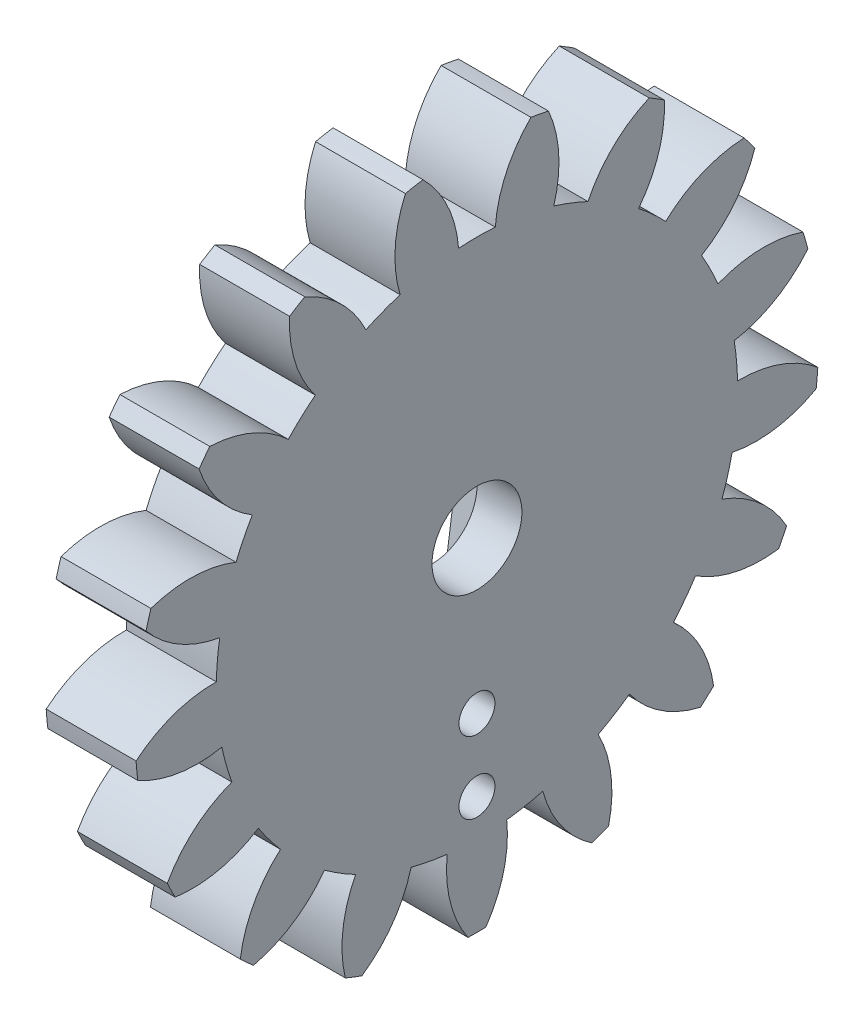
SolidWorks part; units mm, degrees
ref_plane "Plane1" through (0, 0, 0) normal (0, 0, 1) x (1, 0, 0)
ref_plane "Plane2" through (0, 0, 0) normal (0, 1, 0) x (1, 0, 0)
ref_plane "Plane3" through (0, 0, 0) normal (1, 0, 0) x (0, 0, -1)
sketch "HoldingSke" plane through (0, 0, 0) normal (0, 1, 0) x (1, 0, 0)
  line L0 (0, 0) -> (0.4782, -0.1462)
  line L1 (-15, 0) -> (100, 0) construction
  line L2 (0, 0) -> (-2.1039, 2.3779)
  line L3 (0, 0) -> (-11.863, 4.5341)
  line L4 (0, 0) -> (8.2586, 2.5249)
  line L5 (0, 0) -> (-46.8476, -17.4728)
  line L6 (0, 0) -> (-8.2896, -5.593)
  line L7 (-2.1039, 2.3779) -> (8.6588, 51.2067)
  line L8 (-76.2, 54.61) -> (-75.3, 54.61)
  line L9 (-71.009, 38.7566) -> (-53.1078, 45.2721)
  line L10 (-76.2, 71.12) -> (104.1128, 71.12)
  line L11 (0, 0) -> (-10, 0)
  line L12 (-76.2, 101.6) -> (-76.133, 101.6)
  line L13 (24.9733, 27.94) -> (52.9518, 28.4284)
  line L14 (24.9733, 27.94) -> (24.9743, 27.94)
  line L15 (24.9733, 27.94) -> (100.4006, 29.5858)
  line L16 (-63.627, -2) -> (-12.827, -2)
  circle A0 centre (0, 0) radius 2.5
  circle A1 centre (0, 0) radius 14.499
  circle A2 centre (0, 0) radius 37.5
  circle A3 centre (0, 0) radius 2.5
  dimension "Num_teeth" = 17
  dimension "Pitch_radius" = 180.3128
  dimension "Width" = 10
  dimension "Thickness" = 10
sketch "BasProSke" plane through (0, 0, 0) normal (0, 1, 0) x (1, 0, 0)
  line L0 (-10, 0) -> (60, 0) construction
  line L1 (0, 0) -> (0, 19)
  line L2 (0, 0) -> (10, 0)
  line L3 (10, 0) -> (10, 19)
  line L4 (10, 19) -> (0, 19)
  dimension "Thickness" = 10
  dimension "Diameter" = 38
revolve "Base-Revolve" add sketch "BasProSke" angle 360 about L0
sketch "TooCutSke" plane through (0, 0, 0) normal (1, 0, 0) x (0, 0, -1)
  line L1 (0, 0) -> (0, 107) construction
  line L2 (0, 0) -> (-1.6857, 16.9162) construction
  line L3 (0, 0) -> (-6.2247, 33.2991) construction
  line L4 (-1.6857, 16.9162) -> (-3.1123, 16.6495) construction
  arc A0 (1.0204, 14.4631) -> (-1.0204, 14.4631) centre (0, 0) ccw
  arc A1 (3.0261, 18.7832) -> (-3.0261, 18.7832) centre (0, 0) ccw
  circle A2 centre (0, 0) radius 17 construction
  circle A3 centre (0, 0) radius 15.9748 construction
  arc A4 (-1.0204, 14.4631) -> (-3.0261, 18.7832) centre (-7.8003, 13.9409) ccw
  arc A5 (3.0261, 18.7832) -> (1.0204, 14.4631) centre (7.8003, 13.9409) ccw
extrude "ToothCut" cut sketch "TooCutSke" along normal through all
fillet "Breaks" [suppressed] radius 0.04 tangent propagation no
fillet "RootFillets" [suppressed] radius 0.501
pattern_circular "TeethCuts" count 17 every 21.176 about axis through (-10, 0, 0) along (1, 0, 0) of "ToothCut", "RootFillets", "Breaks"
sketch "HubNeaOneSke" plane through (0, 0, 0) normal (-1, 0, 0) x (0, 0, 1)
  circle A0 centre (0, 0) radius 14.499
  dimension "Diameter" = 28.998
extrude "HubNearOne" [suppressed] add sketch "HubNeaOneSke" along normal blind 40.0009
sketch "HubNeaBotSke" plane through (0, 0, 0) normal (-1, 0, 0) x (0, 0, 1)
  circle A0 centre (0, 0) radius 14.499
  dimension "Diameter" = 28.998
extrude "HubNearBoth" [suppressed] add sketch "HubNeaBotSke" along normal blind 20.0004
ref_plane "FarPln" through (10, 0, 0) normal (1, 0, 0) x (0, 0, -1)
sketch "HubFarSke" plane through (10, 0, 0) normal (1, 0, 0) x (0, 0, -1)
  circle A0 centre (0, 0) radius 14.499
  dimension "Diameter" = 28.998
extrude "HubFar" [suppressed] add sketch "HubFarSke" along normal blind 20.0004
sketch "BorSke" plane through (0, 0, 0) normal (1, 0, 0) x (0, 0, -1)
  circle A0 centre (0, 0) radius 2.5
  dimension "Diameter" = 5
extrude "Bore" cut sketch "BorSke" along normal mid plane 100.0017
sketch "KeySke" plane through (0, 0, 0) normal (1, 0, 0) x (0, 0, -1)
  line L0 (-1, 0) -> (-1, 3.4)
  line L1 (-1, 3.4) -> (1, 3.4)
  line L2 (1, 3.4) -> (1, 0)
  line L3 (0, 0) -> (0, 34) construction
  line L4 (-1, 0) -> (1, 0)
  dimension "Width" = 2
extrude "Keyway" [suppressed] cut sketch "KeySke" along normal mid plane 100.0017
pattern_circular "Keyway2" [suppressed] count 2 every 90 about axis through (-10, 0, 0) along (1, 0, 0)
sketch "Sketch1" plane through (0, 0, 0) normal (0, 0, 1) x (1, 0, 0)
  line L1 (-5, 20) -> (5, 20)
  line L2 (-5, 20) -> (-5, -20)
  line L3 (-5, -20) -> (5, -20)
  line L4 (5, 20) -> (5, -20)
  line L5 (-5, 20) -> (5, -20) construction
  line L6 (-5, -20) -> (5, 20) construction
  point P0 (0, 0)
  dimension "D1" = 10
  dimension "D2" = 40
extrude "Cut-Extrude1" cut sketch "Sketch1" against normal blind 20 and the other way blind 20
sketch "Sketch2" plane through (5, 0, 0) normal (-1, 0, 0) x (0, 0, 1)
  line L0 (0, 0) -> (0, -21.0725) construction
  line L1 (-3.961, -0.5571) -> (-2, -14.5)
  line L2 (4, 0) -> (2, -14.5)
  circle A0 centre (0, 0) radius 4
  circle A1 centre (0, -14.5) radius 2
  dimension "D1" = 8
  dimension "D2" = 4
  dimension "D3" = 14.5
extrude "Cut-Extrude3" cut sketch "Sketch2" against normal blind 2.5 contours L0 A1 | A1 L0 | A0 L0 A1 L2 | L0 A0 L1 A1 | L2 A0 region at (5, -7.769, 1.5735) region at (5, -7.7482, -1.5886) region at (5, 0.0003, -0.0021) region at (5, -14.5, 0.8488) region at (5, -14.5, -0.8488)
sketch "Sketch3" plane through (7.5, 0, 0) normal (-1, 0, 0) x (0, 0, 1)
  line L0 (0, 0) -> (0, -12.45) construction
  circle A0 centre (0, -12.45) radius 1
  circle A1 centre (0, -8.45) radius 1
  dimension "D2" = 2
  dimension "D3" = 8.45
  dimension "D1" = 12.45
extrude "Cut-Extrude4" cut sketch "Sketch3" against normal through all
equation "' \"Module@HoldingSke\" = 6.35"
equation "' \"Num_teeth@HoldingSke\" = 12"
equation "' \"Ap@HoldingSke\" =  20"
equation "' \"Ap@HoldingSke\" = 20"
equation "'\"Width@HoldingSke\" = 0.2.5 * 25.4"
equation "' \"Hub_dia@HoldingSke\"= 1 * 25.4"
equation "' \"Hub_dia@HoldingSke\" = 1 * 25.4"
equation "' \"Overall_len@HoldingSke\" = 1.0 * 25.4"
equation "' \"Bore@HoldingSke\" = 0.75 * 25.4"
equation "' \"T_dim@HoldingSke\" = 0.1 * 25.4"
equation "' \"Width@KeySke\" = 0.25 * 25.4"
equation "' \"Show_teeth@HoldingSke\" = 13"
equation "' \"Backlash@HoldingSke\" = 0.009 * 25.4"
equation "' \"Addendum_fac@HoldingSke\" = 1.0"
equation "' \"Dedendum_fac@HoldingSke\" = 1.25"
equation "' \"Dedendum_add@HoldingSke\" = 0.00005 * 25.4"
equation "' \"Clearance_fac@HoldingSke\" = 0.25"
equation "\"Pitch@HoldingSke\" = 1 / \"Module@HoldingSke\""
equation "\"Overcut_dia@TooCutSke\" = (\"Num_teeth@HoldingSke\" + 2 * \"Addendum_fac@HoldingSke\") / \"Pitch@HoldingSke\" + 0.002 * 25.4"
equation "\"Pitch_dia@TooCutSke\" = \"Num_teeth@HoldingSke\" / \"Pitch@HoldingSke\""
equation "\"Base_dia@TooCutSke\" = \"Num_teeth@HoldingSke\" / \"Pitch@HoldingSke\" * cos((\"Ap@HoldingSke\"  * 3.14159265 / 180))"
equation "\"Root_dia@TooCutSke\" = (\"Num_teeth@HoldingSke\" + 2) / \"Pitch@HoldingSke\" - 2 * (\"Addendum_fac@HoldingSke\" + \"Dedendum_fac@HoldingSke\") / \"Pitch@HoldingSke\" - \"Dedendum_add@HoldingSke\" * 2"
equation "\"Half_ang@TooCutSke\" = 180 / \"Num_teeth@HoldingSke\""
equation "\"Half_CT@TooCutSke\" = \"Num_teeth@HoldingSke\" / \"Pitch@HoldingSke\" * sin((3.14159265 / 2 / \"Num_teeth@HoldingSke\")) / 2 - 7 * \"Backlash@HoldingSke\" / 4"
equation "\"Flank_rad@TooCutSke\" = \"Num_teeth@HoldingSke\" / \"Pitch@HoldingSke\" / 5"
equation "\"Radius@RootFillets\" = \"Clearance_fac@HoldingSke\" / \"Pitch@HoldingSke\" + \"Dedendum_add@HoldingSke\""
equation "\"Break_rad@Breaks\" = 0.02 / \"Pitch@HoldingSke\""
equation "\"Thickness@HoldingSke\" = \"Width@HoldingSke\""
equation "\"OAL@HoldingSke\" = \"Thickness@HoldingSke\""
equation "\"MHD@HoldingSke\" = (\"Num_teeth@HoldingSke\" + 2) / \"Pitch@HoldingSke\" - 2 * (\"Addendum_fac@HoldingSke\" + \"Dedendum_fac@HoldingSke\")  / \"Pitch@HoldingSke\" - \"Dedendum_add@HoldingSke\" * 2"
equation "\"MBD@HoldingSke\" = (\"Num_teeth@HoldingSke\" + 2) / \"Pitch@HoldingSke\" - 2 * (\"Addendum_fac@HoldingSke\" + \"Dedendum_fac@HoldingSke\")  / \"Pitch@HoldingSke\" - \"Dedendum_add@HoldingSke\" * 2 - 0.002 * 25.4"
equation "\"MHD@HoldingSke\" = ((sgn( \"MHD@HoldingSke\" - \"Hub_dia@HoldingSke\" )-1)*( \"MHD@HoldingSke\" - \"Hub_dia@HoldingSke\" ))/-2+ \"Hub_dia@HoldingSke\""
equation "\"MBD@HoldingSke\" = ((sgn( \"MBD@HoldingSke\" - \"Bore@HoldingSke\" )-1)*( \"MBD@HoldingSke\" - \"Bore@HoldingSke\" ))/-2+ \"Bore@HoldingSke\""
equation "\"OAL@HoldingSke\" = ((sgn( \"OAL@HoldingSke\" - \"Overall_len@HoldingSke\" )+1)*( \"OAL@HoldingSke\" - \"Overall_len@HoldingSke\" ))/2 + \"Overall_len@HoldingSke\" + 0.000002 * 25.4"
equation "\"Num_teeth@TeethCuts\" = int( \"Show_teeth@HoldingSke\" ) + 1"
equation "\"Num_teeth@TeethCuts\" = ((sgn( \"Num_teeth@TeethCuts\" - \"Num_teeth@HoldingSke\" )-1)*( \"Num_teeth@TeethCuts\" - \"Num_teeth@HoldingSke\" ))/-2+ \"Num_teeth@HoldingSke\""
equation "\"Num_teeth@TeethCuts\" = ((sgn( \"Num_teeth@TeethCuts\" - 2.0)+1)*( \"Num_teeth@TeethCuts\" - 2.0))/2 +2.0"
equation "\"Angle@TeethCuts\" = 360.0 / \"Num_teeth@HoldingSke\""
equation "\"Diameter@BasProSke\" = (\"Num_teeth@HoldingSke\" + 2 * \"Addendum_fac@HoldingSke\") / \"Pitch@HoldingSke\""
equation "\"Thickness@BasProSke\"  = \"Thickness@HoldingSke\""
equation "' \"Fillet_rad@BasProSke\" =  \"Thickness@HoldingSke\" * 0.05"
equation "' \"Fillet_rad@BasProSke\" = \"Thickness@HoldingSke\" * 0.05"
equation "\"MHD@HoldingSke\" = ((sgn( \"MHD@HoldingSke\" - \"Root_dia@TooCutSke\" )-1)*( \"MHD@HoldingSke\" - \"Root_dia@TooCutSke\" ))/-2+ \"Root_dia@TooCutSke\""
equation "\"Diameter@HubNeaOneSke\" = \"MHD@HoldingSke\""
equation "\"Length@HubNearOne\" = \"OAL@HoldingSke\" - \"Thickness@BasProSke\""
equation "\"Diameter@HubNeaBotSke\" = \"MHD@HoldingSke\""
equation "\"Length@HubNearBoth\" = ( \"OAL@HoldingSke\" - \"Thickness@BasProSke\" ) / 2.0"
equation "\"Thickness@FarPln\" = \"Thickness@BasProSke\""
equation "\"Diameter@HubFarSke\" = \"MHD@HoldingSke\""
equation "\"Length@HubFar\" = ( \"OAL@HoldingSke\" - \"Thickness@BasProSke\" ) / 2.0"
equation "\"Diameter@BorSke\" = \"MBD@HoldingSke\""
equation "\"D1@Bore\" = \"OAL@HoldingSke\" * 2.0"
equation "\"D1@Keyway\" = \"OAL@HoldingSke\" * 2.0"
equation "\"Offset@KeySke\" = \"T_dim@HoldingSke\" + \"MBD@HoldingSke\" / 2.0"
